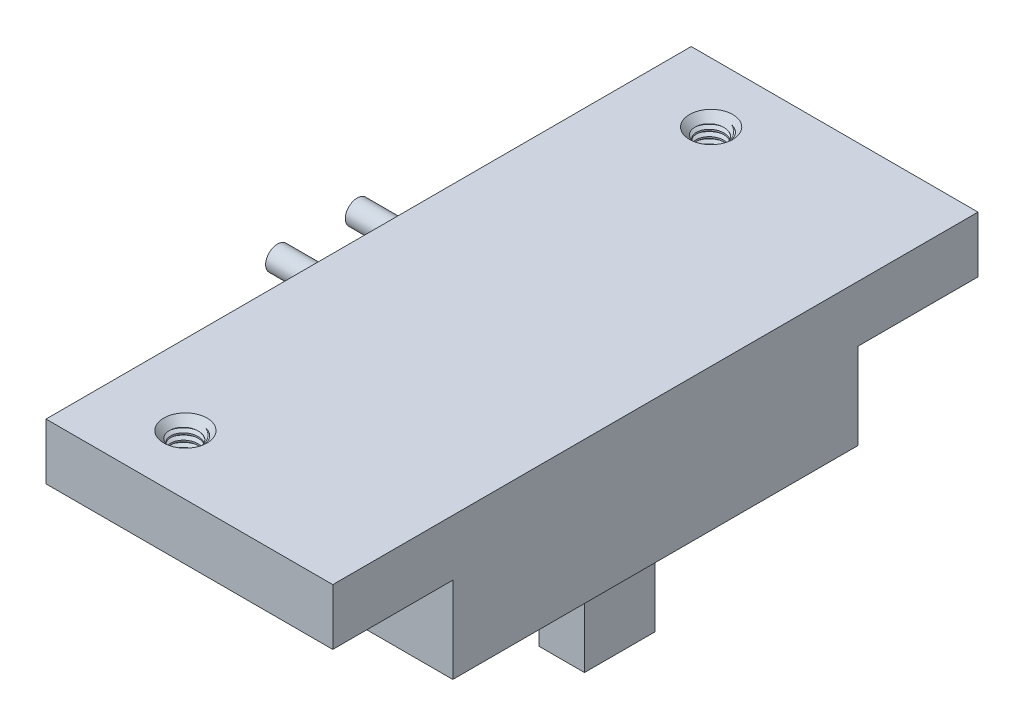
SolidWorks part; units mm, degrees
ref_plane "Front Plane" through (0, 0, 0) normal (0, 0, 1) x (1, 0, 0)
ref_plane "Top Plane" through (0, 0, 0) normal (0, 1, 0) x (1, 0, 0)
ref_plane "Right Plane" through (0, 0, 0) normal (1, 0, 0) x (0, 0, -1)
sketch "Sketch1" plane through (0, 0, 0) normal (0, 1, 0) x (1, 0, 0)
  line L1 (-13.8337, 53.8417) -> (22.1663, 53.8417)
  line L2 (-13.8337, 53.8417) -> (-13.8337, -27.1583)
  line L3 (-13.8337, -27.1583) -> (22.1663, -27.1583)
  line L4 (22.1663, 53.8417) -> (22.1663, -27.1583)
  dimension "D1" = 81
  dimension "D2" = 36
extrude "Boss-Extrude1" add sketch "Sketch1" along normal blind 5
sketch "Sketch2" plane through (0, 0, 0) normal (0, -1, 0) x (1, 0, 0)
  line L0 (-13.8337, -53.8417) -> (-13.8337, 27.1583) construction
  line L1 (-13.8337, 12.0883) -> (22.1663, 12.0883)
  line L2 (-13.8337, 12.0883) -> (-13.8337, -38.7717)
  line L3 (-13.8337, -38.7717) -> (22.1663, -38.7717)
  line L4 (22.1663, 12.0883) -> (22.1663, -38.7717)
  line L5 (22.1663, 27.1583) -> (22.1663, -53.8417) construction
  line L6 (-13.8337, 27.1583) -> (22.1663, 27.1583) construction
  line L7 (22.1663, -53.8417) -> (-13.8337, -53.8417) construction
  dimension "D1" = 15.07
  dimension "D2" = 15.07
extrude "Boss-Extrude2" add sketch "Sketch2" along normal blind 3
sketch "Sketch3" plane through (-13.8337, 0, 0) normal (-1, 0, 0) x (0, 0, 1)
  line L2 (12.0883, -3) -> (-38.7717, -3) construction
  circle A0 centre (-17.9117, 2) radius 1.5
  circle A1 centre (-7.9117, 2) radius 1.5
  dimension "D4" = 3
  dimension "D5" = 3
  dimension "D1" = 5
  dimension "D2" = 10
  dimension "D3" = 20
  dimension "D6" = 5
extrude "Boss-Extrude3" add sketch "Sketch3" along normal blind 6
sketch "Sketch5" plane through (0, -3, 0) normal (0, -1, 0) x (1, 0, 0)
  line L0 (22.1663, -38.7717) -> (22.1663, 12.0883) construction
  line L1 (-13.8337, -38.7717) -> (22.1663, -38.7717)
  line L2 (-13.8337, -38.7717) -> (-13.8337, -24.2717)
  line L3 (-13.8337, -24.2717) -> (22.1663, -24.2717)
  line L4 (22.1663, -38.7717) -> (22.1663, -24.2717)
  line L6 (22.1663, -2.4117) -> (-13.8337, -2.4117)
  line L7 (22.1663, -2.4117) -> (22.1663, 12.0883)
  line L8 (22.1663, 12.0883) -> (-13.8337, 12.0883)
  line L9 (-13.8337, -2.4117) -> (-13.8337, 12.0883)
  dimension "D1" = 14.5
  dimension "D2" = 14.5
extrude "Boss-Extrude4" add sketch "Sketch5" along normal blind 9.85
sketch "Sketch6" plane through (0, -3, 0) normal (0, -1, 0) x (1, 0, 0)
  line L1 (12.1663, -2.4117) -> (22.1663, -2.4117)
  line L2 (12.1663, -2.4117) -> (12.1663, -24.2717)
  line L3 (12.1663, -24.2717) -> (22.1663, -24.2717)
  line L4 (22.1663, -2.4117) -> (22.1663, -24.2717)
  dimension "D1" = 10
extrude "Boss-Extrude5" add sketch "Sketch6" along normal blind 9.85
sketch "Sketch7" plane through (0, -12.85, 0) normal (0, -1, 0) x (1, 0, 0)
  line L1 (17.6799, -8.9298) -> (11.9799, -8.9298)
  line L2 (17.6799, -8.9298) -> (17.6799, -17.7798)
  line L3 (17.6799, -17.7798) -> (11.9799, -17.7798)
  line L4 (11.9799, -8.9298) -> (11.9799, -17.7798)
  dimension "D1" = 8.85
  dimension "D2" = 5.7
extrude "Boss-Extrude6" add sketch "Sketch7" along normal blind 12
sketch "Sketch8" plane through (0, 5, 0) normal (0, 1, 0) x (1, 0, 0)
  line L0 (-13.8337, 53.8417) -> (-3.8337, 53.8417) construction
  line L1 (22.1663, 53.8417) -> (-13.8337, 53.8417) construction
  line L2 (-3.8337, 53.8417) -> (-3.8337, 46.3417) construction
  line L3 (-13.8337, -27.1583) -> (-3.8337, -27.1583) construction
  line L4 (-13.8337, -27.1583) -> (22.1663, -27.1583) construction
  line L5 (-3.8337, -27.1583) -> (-3.8337, -19.6583) construction
  circle A0 centre (-3.8337, 46.3417) radius 2
  circle A1 centre (-3.8337, -19.6583) radius 2
  dimension "D3" = 7.5
  dimension "D1" = 10
  dimension "D2" = 7.5
sketch "Sketch17" plane through (0, 0, 0) normal (0, -1, 0) x (1, 0, 0)
  line L1 (-13.8337, 27.1583) -> (22.1663, 27.1583)
  line L2 (-13.8337, 27.1583) -> (-13.8337, 12.0883)
  line L3 (-13.8337, 12.0883) -> (22.1663, 12.0883)
  line L4 (22.1663, 27.1583) -> (22.1663, 12.0883)
  line L5 (-13.8337, -38.7717) -> (22.1663, -38.7717)
  line L6 (-13.8337, -38.7717) -> (-13.8337, -53.8417)
  line L7 (-13.8337, -53.8417) -> (22.1663, -53.8417)
  line L8 (22.1663, -38.7717) -> (22.1663, -53.8417)
extrude "Boss-Extrude7" add sketch "Sketch17" along normal blind 2.05
hole_wizard "#8-32 Tapped Hole2" positions "Sketch16" profile "Sketch15" tap size "#8-32" standard "ANSI Inch"
sketch "Sketch16" plane through (0, 5, 0) normal (0, 1, 0) x (1, 0, 0)
  point P0 (-3.8337, 46.3417)
  point P3 (-3.8337, -19.6583)
sketch "Sketch15" plane through (-3.8337, 5, -46.3417) normal (1, 0, 0) x (0, 0, 1)
  line L0 (0, 0) -> (0, 12)
  line L1 (0, 12) -> (1.7272, 10.9622)
  line L2 (1.7272, 10.9622) -> (1.7272, 0.9906)
  line L3 (1.7272, 0.9906) -> (2.7178, 0)
  line L5 (2.7178, 0) -> (0, 0)
  line L6 (-1.7272, 0.9906) -> (-2.7178, 0) construction
  line L10 (0, 12) -> (-1.7272, 10.9622) construction
  line L11 (0, -6.35) -> (0, 107.95) construction
  dimension "Tap Drill Dia." = 3.4544
  dimension "Tap Drill Depth" = 12
  dimension "Near C'Sink Dia." = 5.4356
  dimension "Near C'Sink Angle" = 90
  dimension "Drill Angle" = 118
cosmetic thread "Hole Thread1" parameters "D1"=8.33, "D2"=4.1656
cosmetic thread "Hole Thread2" parameters "D1"=8.33, "D2"=4.1656
thread "Thread4" pitch 0.7937 method cut profile "Thread Profile10" start angle 0, offset 1, length 10, pitch 0.7937, diameter 3.4544
ref_plane "Plane10" through (-5.5609, 5.0094, -46.3417) normal (0, 0, 1) x (-1, 0, 0)
sketch "Thread Profile10" plane through (-5.5609, 5.0094, -46.3417) normal (0, 0, 1) x (-1, 0, 0)
  line L0 (0, 0) -> (0, 0.7937) construction
  line L1 (0, 0) -> (0.4296, 0.248)
  line L2 (0.4296, 0.248) -> (0.4296, 0.3473)
  line L3 (0.4296, 0.3473) -> (0, 0.5953)
  line L4 (0.4296, 0.2977) -> (0, 0.2977) construction
  line L11 (0, 0) -> (0, 0.5953)
  point P2 (0, 0)
  dimension "Pitch" = 0.7937
  dimension "Profile_Angle" = 60
  dimension "Profile_Land" = 0.0992
  dimension "Profile_Height" = 0.4296
thread "Thread5" pitch 0.7937 method cut profile "Thread Profile11" start angle 0, offset 1, length 10, pitch 0.7937, diameter 3.4544
ref_plane "Plane11" through (-5.5609, 5.0094, 19.6583) normal (0, 0, 1) x (-1, 0, 0)
sketch "Thread Profile11" plane through (-5.5609, 5.0094, 19.6583) normal (0, 0, 1) x (-1, 0, 0)
  line L0 (0, 0) -> (0, 0.7937) construction
  line L1 (0, 0) -> (0.4296, 0.248)
  line L2 (0.4296, 0.248) -> (0.4296, 0.3473)
  line L3 (0.4296, 0.3473) -> (0, 0.5953)
  line L4 (0.4296, 0.2977) -> (0, 0.2977) construction
  line L11 (0, 0) -> (0, 0.5953)
  point P2 (0, 0)
  dimension "Pitch" = 0.7937
  dimension "Profile_Angle" = 60
  dimension "Profile_Land" = 0.0992
  dimension "Profile_Height" = 0.4296
